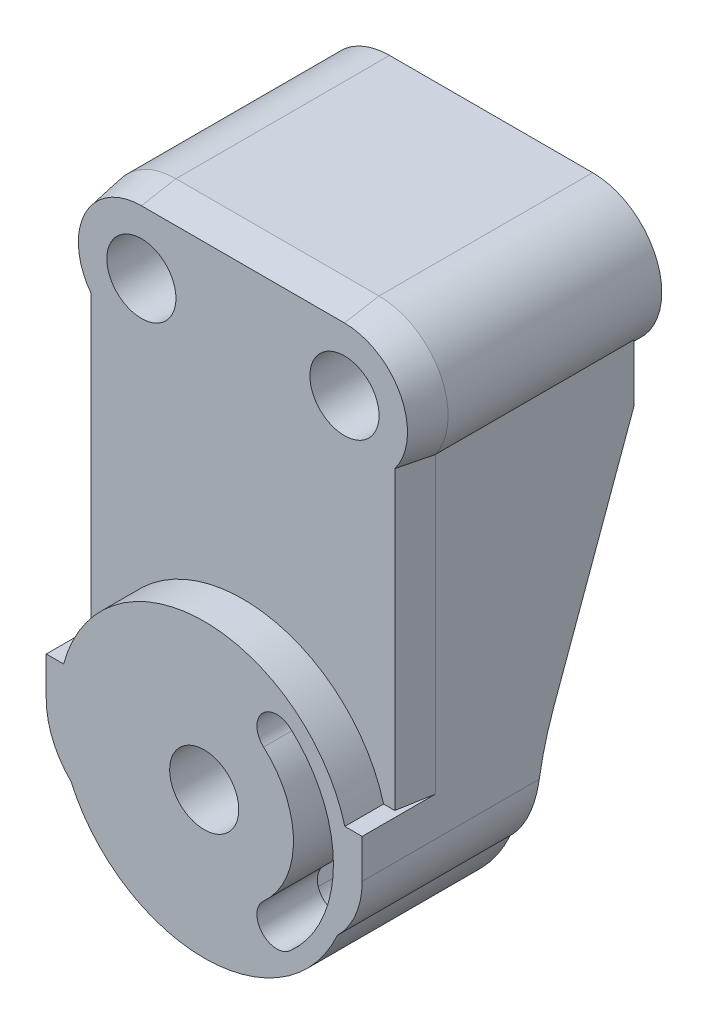
SolidWorks part; units mm, degrees
ref_plane "Front Plane" through (0, 0, 0) normal (0, 0, 1) x (1, 0, 0)
ref_plane "Top Plane" through (0, 0, 0) normal (0, 1, 0) x (1, 0, 0)
ref_plane "Right Plane" through (0, 0, 0) normal (1, 0, 0) x (0, 0, -1)
sketch "Sketch39" plane through (0, 0, 0) normal (0, 0, -1) x (-1, 0, 0)
  line L0 (-37.3063, 244.5512) -> (37.3063, 244.5512) construction
  line L1 (-37.3063, 269.9512) -> (37.3063, 269.9512)
  line L5 (-58.039, 229.8776) -> (-58.039, 107.4974)
  line L7 (58.039, 229.8776) -> (58.039, 107.4974)
  line L11 (0, 244.5512) -> (0, 107.6452) construction
  line L12 (-101.2355, 85.8012) -> (92.7589, 85.8012) construction
  line L13 (55, 0) -> (-55, 0) construction
  line L14 (0, 55) -> (0, -55) construction
  arc A0 (-48.9403, 85.8012) -> (48.9403, 85.8012) centre (0, 107.6452) ccw
  arc A1 (-37.3063, 269.9512) -> (-58.039, 229.8776) centre (-37.3063, 244.5512) ccw
  arc A2 (58.039, 229.8776) -> (37.3063, 269.9512) centre (37.3063, 244.5512) ccw
  circle A3 centre (-37.3063, 244.5512) radius 12.7
  circle A4 centre (37.3063, 244.5512) radius 12.7
  arc A5 (-58.039, 107.4974) -> (-48.9403, 85.8012) centre (-27.622, 107.4974) ccw
  arc A6 (58.039, 107.4974) -> (48.9403, 85.8012) centre (27.622, 107.4974) cw
  dimension "D1" = 107.188
  dimension "D3" = 125.4125
  dimension "D4" = 215.9
  dimension "D5" = 25.4
  dimension "D12" = 31.75
  dimension "D7" = 30.417
  dimension "D2" = 25.4
  dimension "D6" = 116.078
  dimension "D8" = 107.6452
  dimension "D10" = 74.6125
extrude "Boss-Extrude16" add sketch "Sketch39" along normal blind 105.41
ref_plane "Plane4" through (0, 0, 0) normal (1, 0, 0) x (0, 0, -1)
sketch "Sketch40" plane through (0, 0, 0) normal (1, 0, 0) x (0, 0, -1)
  line L0 (99.949, 208.9912) -> (70.4697, 127.9976)
  line L1 (105.41, 229.8776) -> (99.949, 229.8776)
  line L2 (105.41, 229.8776) -> (0, 229.8776) construction
  line L3 (99.949, 229.8776) -> (99.949, 208.9912)
  line L5 (63.5, 88.4703) -> (63.5, 54.0512)
  line L6 (0, 54.0512) -> (105.41, 54.0512) construction
  line L7 (63.5, 54.0512) -> (105.41, 54.0512)
  line L8 (105.41, 54.0512) -> (105.41, 229.8776)
  line L10 (105.41, 269.9512) -> (0, 269.9512) construction
  arc A0 (70.4697, 127.9976) -> (63.5, 88.4703) centre (179.07, 88.4703) ccw
  point P9 (63.5, 108.8484)
  dimension "D5" = 20
  dimension "D6" = 115.57
  dimension "D1" = 5.461
  dimension "D2" = 41.91
  dimension "D3" = 215.9
  dimension "D4" = 60.96
extrude "Cut-Extrude13" cut sketch "Sketch40" against normal through all both and the other way through all
sketch "Sketch41" plane through (0, 0, -105.41) normal (0, 0, -1) x (-1, 0, 0)
  line L0 (-37.3063, 244.5512) -> (37.3063, 244.5512) construction
  line L1 (-37.3063, 269.9512) -> (37.3063, 269.9512)
  line L2 (-37.3063, 219.1512) -> (37.3063, 219.1512)
  arc A0 (-37.3063, 269.9512) -> (-37.3063, 219.1512) centre (-37.3063, 244.5512) ccw
  arc A1 (37.3063, 219.1512) -> (37.3063, 269.9512) centre (37.3063, 244.5512) ccw
  arc A2 (58.039, 229.8776) -> (37.3063, 269.9512) centre (37.3063, 244.5512) ccw construction
  circle A3 centre (-37.3063, 244.5512) radius 12.7
  circle A4 centre (37.3063, 244.5512) radius 12.7
  circle A5 centre (-37.3063, 244.5512) radius 12.7 construction
  circle A6 centre (37.3063, 244.5512) radius 12.7 construction
  point P4 (0, 244.5512)
extrude "Boss-Extrude17" add sketch "Sketch41" against normal up to surface (5.461 mm away) up to face at (0, 219.4344, -99.949)
sketch "Sketch42" plane through (0, 0, -105.41) normal (0, 0, -1) x (-1, 0, 0)
  circle A0 centre (0, 107.6452) radius 53.594
  arc A1 (-48.9403, 85.8012) -> (48.9403, 85.8012) centre (0, 107.6452) ccw construction
extrude "Cut-Extrude14" cut sketch "Sketch42" against normal up to surface (41.91 mm away) up to face at (0, 79.1804, -63.5)
sketch "Sketch43" plane through (0, 0, -63.5) normal (0, 0, -1) x (-1, 0, 0)
  line L0 (-17.1406, 142.3385) -> (-8.3201, 124.4855)
  line L1 (0, 146.3104) -> (0, 68.98) construction
  line L2 (-8.3201, 90.8049) -> (-17.1406, 72.9519)
  line L3 (0, 107.6452) -> (-142.8632, 107.6452) construction
  circle A0 centre (0, 107.6452) radius 12.7
  arc A3 (-33.7911, 145.5768) -> (-33.7911, 69.7136) centre (0, 107.6452) ccw
  arc A4 (-9.3056, 94.7835) -> (-8.3201, 90.8049) centre (-11.1667, 92.2112) cw
  arc A5 (-8.3201, 124.4855) -> (-9.3056, 120.5069) centre (-11.1667, 123.0792) cw
  arc A6 (-33.7911, 69.7136) -> (-17.1406, 72.9519) centre (-26.6992, 77.6745) ccw
  arc A7 (-33.7911, 145.5768) -> (-17.1406, 142.3385) centre (-26.6992, 137.6159) cw
  arc A9 (-9.3056, 120.5069) -> (-9.3056, 94.7835) centre (0, 107.6452) ccw
  point P6 (0, 0)
  point P7 (0, 0)
  point P23 (0, 0)
  dimension "D1" = 25.4
  dimension "D2" = 26.292
  dimension "D3" = 26.292
  dimension "D4" = 3.175
  dimension "D5" = 15.875
  dimension "D7" = 50.8
  dimension "D6" = 59.9414
extrude "Cut-Extrude15" cut sketch "Sketch43" against normal blind 41.275
sketch "Sketch57" plane through (0, 0, 0) normal (0, 0, 1) x (1, 0, 0)
  line L0 (-58.039, 121.8184) -> (-51.6859, 121.8184)
  line L1 (51.6859, 121.8184) -> (58.039, 121.8184)
  line L3 (37.3063, 269.9512) -> (-37.3063, 269.9512)
  line L4 (-58.039, 229.8776) -> (-58.039, 107.4974)
  line L5 (58.039, 107.4974) -> (58.039, 229.8776)
  line L6 (37.3063, 269.9512) -> (-37.3063, 269.9512)
  line L7 (-58.039, 229.8776) -> (-58.039, 121.8184)
  line L8 (58.039, 121.8184) -> (58.039, 229.8776)
  arc A0 (51.6859, 121.8184) -> (-51.6859, 121.8184) centre (0, 107.6452) ccw
  arc A1 (-48.9403, 85.8012) -> (48.9403, 85.8012) centre (0, 107.6452) ccw construction
  arc A6 (58.039, 229.8776) -> (37.3063, 269.9512) centre (37.3063, 244.5512) ccw
  arc A7 (-37.3063, 269.9512) -> (-58.039, 229.8776) centre (-37.3063, 244.5512) ccw
  arc A8 (-58.039, 107.4974) -> (-48.9403, 85.8012) centre (-27.622, 107.4974) ccw
  arc A9 (-48.9403, 85.8012) -> (48.9403, 85.8012) centre (0, 107.6452) ccw
  arc A10 (48.9403, 85.8012) -> (58.039, 107.4974) centre (27.622, 107.4974) ccw
  arc A11 (58.039, 229.8776) -> (37.3063, 269.9512) centre (37.3063, 244.5512) ccw
  arc A12 (-37.3063, 269.9512) -> (-58.039, 229.8776) centre (-37.3063, 244.5512) ccw
  point P3 (54.8625, 121.8184)
  dimension "D3" = 14.1732
  dimension "D1" = 0
extrude "Cut-Extrude25" cut sketch "Sketch57" against normal blind 14.224
chamfer "Chamfer1" distance 12.7 angle 10 5 edges at (58.039, 175.848, -14.224) (59.8658, 256.2228, -14.224) (0, 269.9512, -14.224) (-59.8658, 256.2228, -14.224) (-58.039, 175.848, -14.224) first distance on face at (58.039, 156.9374, -45.4277) first distance on face at (50.7002, 240.2909, -73.1943) first distance on face at (0, 269.9512, -59.817) first distance on face at (-50.7002, 240.2909, -73.1943) first distance on face at (-58.039, 156.9374, -45.4277)
sketch "Sketch46" plane through (0, 0, -105.41) normal (0, 0, -1) x (-1, 0, 0)
  line L0 (-56.1544, 206.4512) -> (-56.1544, 123.5202)
  line L1 (-56.1544, 123.5202) -> (-51.1889, 123.5202)
  line L2 (56.1544, 206.4512) -> (56.1544, 123.5202)
  line L3 (56.1544, 123.5202) -> (51.1889, 123.5202)
  line L6 (-49.8717, 219.1512) -> (-32.0303, 219.1512)
  line L8 (0, 107.6452) -> (-37.3063, 244.5512) construction
  line L9 (0, 107.6452) -> (37.3063, 244.5512) construction
  line L10 (-32.0303, 219.1512) -> (-16.0886, 160.6489)
  line L11 (32.0303, 219.1512) -> (16.0909, 160.6571)
  line L12 (28.7395, 219.1512) -> (13.0276, 161.4918)
  line L13 (-28.7395, 219.1512) -> (-13.0253, 161.4836)
  line L14 (32.0303, 219.1512) -> (49.8717, 219.1512)
  line L15 (-28.7395, 219.1512) -> (28.7395, 219.1512)
  line L16 (-56.1544, 206.4512) -> (-49.8717, 219.1512)
  line L17 (56.1544, 206.4512) -> (49.8717, 219.1512)
  line L18 (-37.3063, 219.1512) -> (37.3063, 219.1512) construction
  line L19 (-37.3063, 244.5512) -> (-49.8717, 219.1512) construction
  line L20 (37.3063, 244.5512) -> (49.8717, 219.1512) construction
  line L21 (0, 107.6452) -> (0, 194.7411) construction
  line L22 (-382.5415, 107.6452) -> (382.5415, 107.6452) construction
  arc A0 (51.1889, 123.5202) -> (16.3794, 158.6749) centre (0, 107.6452) ccw
  arc A1 (-48.9403, 85.8012) -> (48.9403, 85.8012) centre (0, 107.6452) ccw construction
  arc A2 (-16.3734, 158.6769) -> (-51.1889, 123.5202) centre (0, 107.6452) ccw
  arc A3 (11.7733, 159.93) -> (-11.7795, 159.9287) centre (0, 107.6452) ccw
  arc A4 (-16.0886, 160.6489) -> (-16.3734, 158.6769) centre (-14.0904, 159.3538) ccw
  arc A5 (-11.7795, 159.9287) -> (-13.0253, 161.4836) centre (-14.0904, 159.3538) ccw
  arc A6 (16.3794, 158.6749) -> (16.0909, 160.6571) centre (14.0904, 159.3538) ccw
  arc A7 (13.0276, 161.4918) -> (11.7733, 159.93) centre (14.0904, 159.3538) ccw
  point P13 (-53.6716, 123.5202)
  point P20 (53.6716, 123.5202)
  point P23 (-14.0904, 159.3538)
  point P38 (14.0904, 159.3538)
  dimension "D1" = 15.875
  dimension "D7" = 4.7625
  dimension "D8" = 4.7752
  dimension "D2" = 56.1544
  dimension "D4" = 3.175
  dimension "D5" = 3.175
  dimension "D6" = 12.7
extrude "Cut-Extrude18" cut sketch "Sketch46" against normal blind 63.5
sketch "Sketch47" plane through (0, 0, 0) normal (1, 0, 0) x (0, 0, -1)
  line L0 (99.949, 219.1512) -> (63.5, 161.0855)
  line L1 (63.5, 161.0855) -> (105.41, 161.0855)
  line L2 (105.41, 161.0855) -> (105.41, 219.1512)
  line L3 (105.41, 219.1512) -> (99.949, 219.1512)
  line L4 (63.5, 107.1105) -> (602.8493, 107.1105) construction
  line L5 (63.5, 54.0512) -> (63.5, 85.8012) construction
  dimension "D1" = 107.1105
  dimension "D2" = 53.975
revolve "Cut-Revolve4" cut sketch "Sketch47" angle 45 mid plane about L4
sketch "Sketch52" plane through (0, 0, -63.5) normal (0, 0, -1) x (-1, 0, 0)
  line L3 (0, 107.6452) -> (0, 177.4878) construction
  line L4 (-56.1544, 123.5202) -> (-51.1889, 123.5202)
  line L5 (-51.1889, 123.5202) -> (-56.1544, 123.5202) construction
  line L6 (51.1889, 123.5202) -> (56.1544, 123.5202)
  arc A3 (50.8764, 90.7957) -> (51.1889, 123.5202) centre (0, 107.6452) ccw
  arc A4 (-16.3734, 158.6769) -> (-51.1889, 123.5202) centre (0, 107.6452) ccw construction
  arc A5 (-56.1544, 123.5202) -> (-50.8764, 90.7957) centre (47.9341, 123.5202) ccw
  arc A6 (-51.1889, 123.5202) -> (-50.8764, 90.7957) centre (0, 107.6452) ccw
  arc A7 (56.1544, 123.5202) -> (50.8764, 90.7957) centre (-47.9341, 123.5202) cw
extrude "Cut-Extrude22" cut sketch "Sketch52" along normal up to next
sketch "Sketch53" plane through (0, 0, -63.5) normal (0, 0, -1) x (-1, 0, 0)
  circle A0 centre (0, 107.6452) radius 12.7
  circle A1 centre (0, 107.6452) radius 12.7 construction
extrude "Cut-Extrude23" cut sketch "Sketch53" against normal through all
sketch "Sketch54" plane through (0, 0, -22.225) normal (0, 0, -1) x (-1, 0, 0)
  line L2 (0, 107.6452) -> (-35.4231, 107.6452) construction
  arc A0 (-26.6992, 77.6745) -> (-26.6992, 137.6159) centre (0, 107.6452) cw construction
  arc A1 (-31.582, 143.097) -> (-31.582, 72.1934) centre (0, 107.6452) ccw
  arc A2 (-21.8164, 132.1348) -> (-21.8164, 83.1556) centre (0, 107.6452) ccw
  arc A3 (-21.8164, 132.1348) -> (-31.582, 143.097) centre (-26.6992, 137.6159) ccw
  arc A4 (-31.582, 72.1934) -> (-21.8164, 83.1556) centre (-26.6992, 77.6745) ccw
  circle A5 centre (0, 107.6452) radius 12.7 construction
  point P3 (-40.1384, 107.6452)
  dimension "D1" = 7.3406
  dimension "D2" = 59.9414
extrude "Cut-Extrude24" cut sketch "Sketch54" against normal through all
ref_axis "Axis1" through (37.3063, 244.5512, -105.41) along (0, 0, 1)
ref_axis "Axis2" through (-37.3063, 244.5512, -105.41) along (0, 0, 1)
sketch "Sketch56" plane through (0, 0, -63.5) normal (0, 0, -1) x (-1, 0, 0)
  arc A0 (-26.6992, 137.6159) -> (-26.6992, 77.6745) centre (0, 107.6452) ccw construction
  arc A1 (-31.582, 72.1934) -> (-21.8164, 83.1556) centre (-26.6992, 77.6745) ccw construction
  point P5 (0, 0)
  dimension "D1" = 40.1384
ref_axis "Axis3" through (0, 107.6452, 0) along (0, 0, -1)
